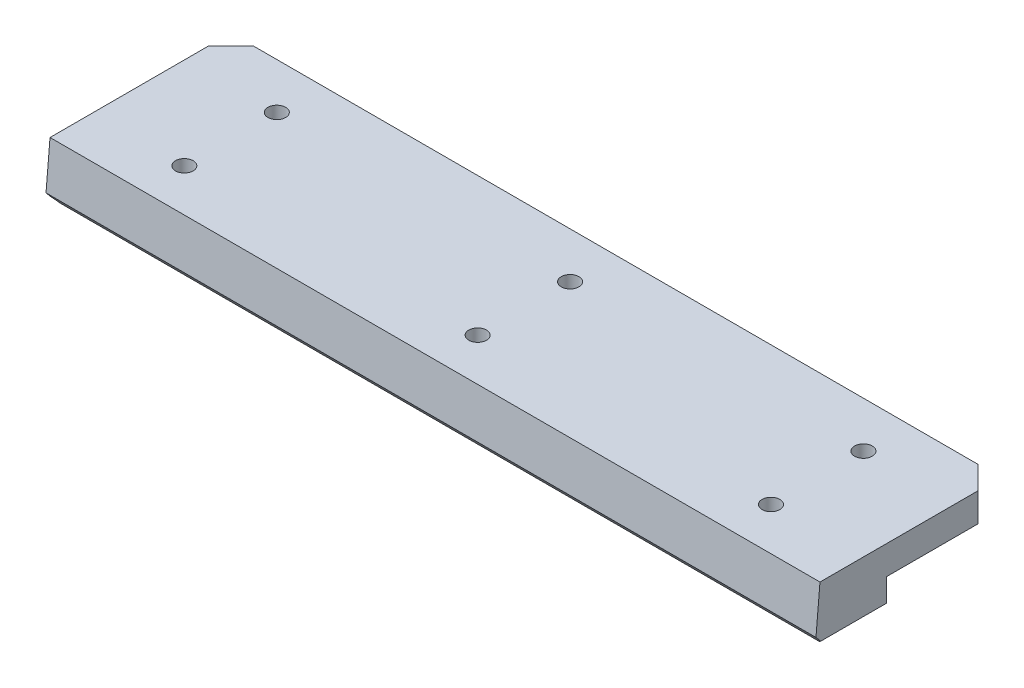
SolidWorks part; units mm, degrees
material "PET"
ref_plane "Front Plane" through (0, 0, 0) normal (0, 0, 1) x (1, 0, 0)
ref_plane "Top Plane" through (0, 0, 0) normal (0, 1, 0) x (1, 0, 0)
ref_plane "Right Plane" through (0, 0, 0) normal (1, 0, 0) x (0, 0, -1)
sketch "Sketch1" plane through (0, 0, 0) normal (1, 0, 0) x (0, 0, -1)
  line L1 (12.7, -4.7625) -> (-12.7, -4.7625)
  line L2 (12.7, -4.7625) -> (12.7, 4.7625)
  line L3 (12.7, 4.7625) -> (-12.7, 4.7625)
  line L4 (-12.7, -4.7625) -> (-12.7, 4.7625)
  line L5 (12.7, -4.7625) -> (-12.7, 4.7625) construction
  line L6 (12.7, 4.7625) -> (-12.7, -4.7625) construction
  point P0 (0, 0)
  dimension "D1" = 9.525
  dimension "D2" = 25.4
extrude "Boss-Extrude1" add sketch "Sketch1" along normal mid plane 213.36
sketch "Sketch2" plane through (-106.68, 0, 0) normal (-1, 0, 0) x (0, 0, 1)
  line L0 (12.7, 4.7625) -> (37.438, 4.7625)
  line L1 (12.7, 4.7625) -> (12.7, -4.7625) construction
  line L2 (37.438, 4.7625) -> (38.829, -11.1363)
  line L4 (38.829, -11.1363) -> (12.7, -11.1363)
  line L9 (12.7, -11.1363) -> (12.7, 4.7625)
  line L10 (-12.7, 4.7625) -> (12.7, 4.7625) construction
  line L11 (25.5674, 149.1875) -> (39.494, -9.9944) construction
  line L12 (19.05, -11.1363) -> (38.1, -11.1363) construction
  dimension "D1" = 0.762
extrude "Boss-Extrude2" add sketch "Sketch2" against normal through all
chamfer "Chamfer1" distance 6.35 angle 45 4 edges at (106.68, -7.9494, 12.7) (106.68, 0, -12.7) (-106.68, 0, -12.7) (-106.68, -7.9494, 12.7)
chamfer "Chamfer2" distance 3.175 angle 45 1 edges at (0, -11.1363, 38.829) first distance on face at (0, -3.1869, 38.1335)
hole_wizard "#8 Clearance Hole1" positions "Sketch3" profile "Sketch4" hole size "#8" standard "ANSI Inch" end condition up to next
sketch "Sketch3" plane through (0, -11.1363, 0) normal (0, -1, 0) x (-1, 0, 0)
  line L0 (0, -38.5523) -> (0, -12.7) construction
  line L1 (106.68, -38.5523) -> (-106.68, -38.5523) construction
  line L2 (-100.33, -12.7) -> (100.33, -12.7) construction
  line L3 (0, -12.7) -> (0, 12.7) construction
  line L4 (-100.33, 12.7) -> (100.33, 12.7) construction
  line L6 (0, 0) -> (106.68, 0) construction
  line L7 (106.68, -19.05) -> (106.68, 6.35) construction
  line L9 (0, -25.6261) -> (106.68, -25.6261) construction
  line L10 (106.68, -19.05) -> (106.68, -35.8983) construction
  point P12 (0, 0)
  point P19 (0, -25.6261)
  point P24 (81.28, -25.6261)
  point P26 (81.28, 0)
  point P33 (0, 0)
  point P34 (0, 0)
  point P35 (-81.28, 0)
  point P36 (-81.28, -25.6261)
  dimension "D1" = 25.4
sketch "Sketch4" plane through (81.28, -11.1363, 25.6261) normal (1, 0, 0) x (0, 0, -1)
  line L0 (0, 0) -> (0, 15.8988)
  line L1 (0, 15.8988) -> (2.4574, 15.8988)
  line L2 (2.4574, 15.8988) -> (2.4574, 0)
  line L5 (2.4574, 0) -> (0, 0)
  line L11 (0, -6.35) -> (0, 107.95) construction
  dimension "Thru Hole Dia." = 4.9149
  dimension "Thru Hole Depth" = 15.8988
chamfer "Chamfer3" distance 1.5875 angle 45 10 edges at (-106.68, -4.7625, 6.35) (-103.505, -4.7625, -9.525) (0, -4.7625, -12.7) (103.505, -4.7625, -9.525) (106.68, -4.7625, 6.35) (106.68, -11.1363, 27.4741) (103.505, -11.1363, 15.875) (0, -11.1363, 12.7) (-103.505, -11.1363, 15.875) (-106.68, -11.1363, 27.4741)
